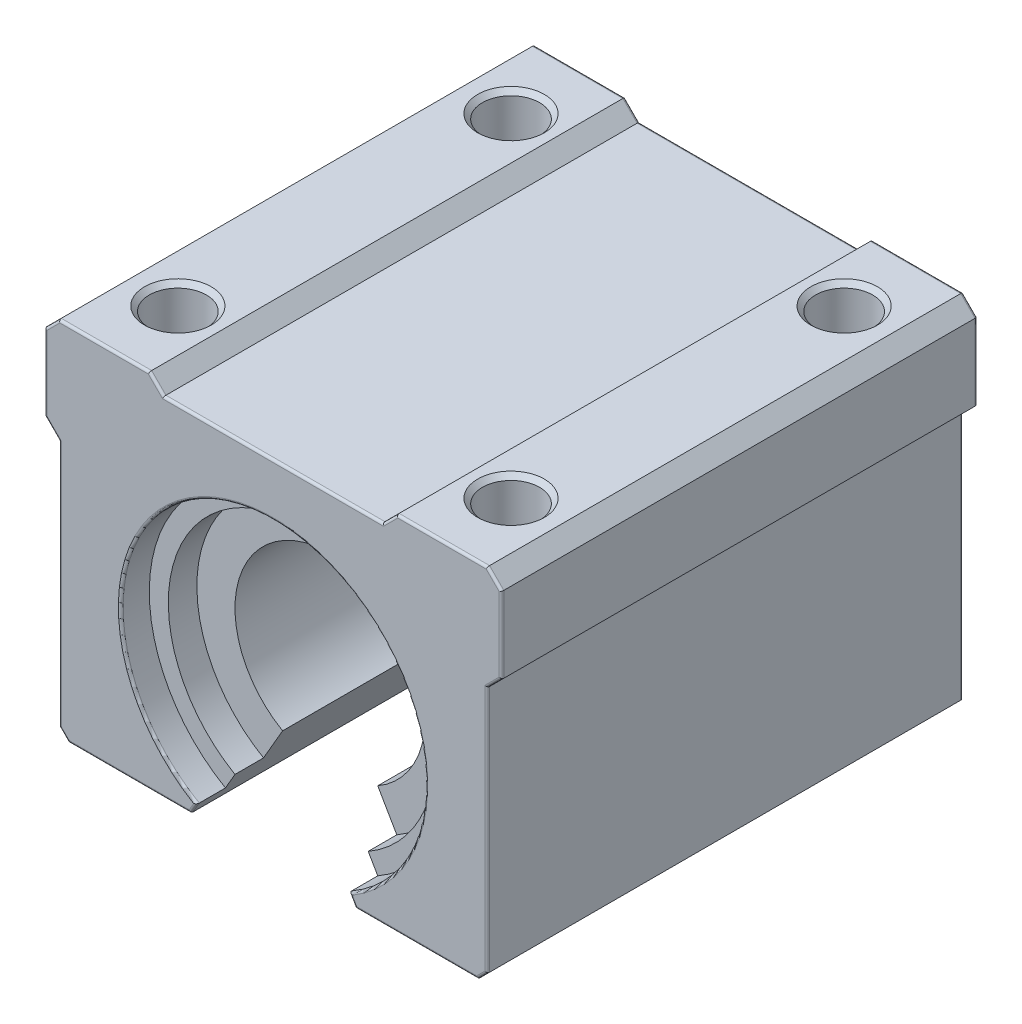
SolidWorks part; units mm, degrees
ref_plane "Front Plane" through (0, 0, 0) normal (0, 0, 1) x (1, 0, 0)
ref_plane "Top Plane" through (0, 0, 0) normal (0, 1, 0) x (1, 0, 0)
ref_plane "Right Plane" through (0, 0, 0) normal (1, 0, 0) x (0, 0, -1)
sketch "Sketch1" plane through (0, 0, 0) normal (0, 0, 1) x (1, 0, 0)
  line L0 (0, 29.1887) -> (0, -22.3517) construction
  line L1 (-34.9739, 0) -> (34.4479, 0) construction
  line L2 (-22.5, 12) -> (-22.5, -15)
  line L3 (24, 12) -> (22.5, 12)
  line L4 (24, 12) -> (24, 23)
  line L5 (24, 23) -> (11.5, 23)
  line L6 (-24, 12) -> (-24, 23)
  line L7 (24, 12) -> (-24, 23) construction
  line L8 (24, 23) -> (-24, 12) construction
  line L9 (-22.5, -15) -> (22.5, -15)
  line L10 (22.5, 12) -> (22.5, -15)
  line L11 (-22.5, 12) -> (-24, 12)
  line L12 (11.5, 21.5) -> (-11.5, 21.5)
  line L13 (-11.5, 21.5) -> (-11.5, 23)
  line L14 (11.5, 21.5) -> (11.5, 23)
  line L15 (-11.5, 23) -> (-24, 23)
  circle A0 centre (0, 0) radius 10 construction
  point P7 (0, 17.5)
  point P18 (0, -15)
  point P22 (0, 21.5)
  dimension "D1" = 20
  dimension "D4" = 23
  dimension "D2" = 48
  dimension "D3" = 11
  dimension "D5" = 38
  dimension "D6" = 22.5
  dimension "D7" = 23
  dimension "D8" = 1.5
  dimension "D9" = 1.5
extrude "Boss-Extrude2" add sketch "Sketch1" along normal mid plane 50
chamfer "Chamfer3" distance 1.5 angle 45 6 edges at (24, 23, 0) (24, 12, 0) (11.5, 23, 0) (-11.5, 23, 0) (-24, 12, 0) (-24, 23, 0)
chamfer "Chamfer4" distance 1 angle 45 2 edges at (22.5, -15, 0) (-22.5, -15, 0)
sketch "Sketch3" plane through (0, 21.5, 0) normal (0, 1, 0) x (1, 0, 0)
  line L0 (0, 31.926) -> (0, -36.2484) construction
  line L1 (42.0099, 0) -> (-40.1024, 0) construction
  circle A0 centre (-17.5, 17.5) radius 3
  circle A1 centre (17.5, 17.5) radius 3
  circle A2 centre (17.5, -17.5) radius 3
  circle A3 centre (-17.5, -17.5) radius 3
  dimension "D1" = 6
  dimension "D2" = 35
  dimension "D3" = 35
extrude "Cut-Extrude6" cut sketch "Sketch3" against normal blind 10.5 and the other way up to next
sketch "Sketch4" plane through (0, 0, 25) normal (0, 0, 1) x (1, 0, 0)
  circle A0 centre (0, 0) radius 10
  dimension "D1" = 20
extrude "Cut-Extrude8" cut sketch "Sketch4" against normal through all both
sketch "Sketch6" plane through (0, 0, 25) normal (0, 0, 1) x (1, 0, 0)
  line L0 (0, 22.6334) -> (0, -18.7712) construction
  line L1 (9.0802, -15.7273) -> (-9.0802, -15.7273)
  line L2 (-9.0802, -15.7273) -> (-5, -8.6603)
  line L3 (-5, -8.6603) -> (5, -8.6603)
  line L4 (9.0802, -15.7273) -> (5, -8.6603)
  line L5 (24, 13.5) -> (24, 21.5) construction
  circle A1 centre (0, 0) radius 10 construction
  point P10 (0, -15.7273)
  point P11 (0, -8.6603)
  dimension "D1" = 10
  dimension "D2" = 60
  dimension "D3" = 14.9198
extrude "Cut-Extrude9" cut sketch "Sketch6" against normal through all both
sketch "Sketch7" plane through (0, 0, 25) normal (0, 0, 1) x (1, 0, 0)
  circle A0 centre (0, 0) radius 16
  dimension "D1" = 32
extrude "Cut-Extrude10" cut sketch "Sketch7" against normal blind 3
sketch "Sketch8" plane through (0, 0, -25) normal (0, 0, -1) x (-1, 0, 0)
  circle A0 centre (0, 0) radius 16
  dimension "D1" = 32
extrude "Cut-Extrude11" cut sketch "Sketch8" against normal blind 3
sketch "Sketch9" plane through (0, 0, 22) normal (0, 0, 1) x (1, 0, 0)
  circle A0 centre (0, 0) radius 14
  dimension "D1" = 28
extrude "Cut-Extrude12" cut sketch "Sketch9" against normal blind 3
sketch "Sketch10" plane through (0, 0, -22) normal (0, 0, -1) x (-1, 0, 0)
  circle A0 centre (0, 0) radius 14
  dimension "D1" = 28
extrude "Cut-Extrude13" cut sketch "Sketch10" against normal blind 3
chamfer "Chamfer5" distance 0.5 angle 45 4 edges at (17.5, 23, 14.5) (17.5, 23, -20.5) (-14.5, 23, -17.5) (-14.5, 23, 17.5)
fillet "Fillet1" radius 0.25 20 edges at (15.0801, -15, -25) (22, -14.5, -25) (22.5, -1, -25) (23.25, 12.75, -25) (24, 17.5, -25) (23.25, 22.25, -25) (17.75, 23, -25) (12.25, 22.25, -25) (0, 21.5, -25) (-12.25, 22.25, -25) (-17.75, 23, -25) (-23.25, 22.25, -25) (-24, 17.5, -25) (-23.25, 12.75, -25) (-22.5, -1, -25) (-22, -14.5, -25) (-15.0801, -15, -25) (-8.3301, -14.4282, -25) (0, 16, -25) (8.3301, -14.4282, -25)
fillet "Fillet3" radius 0.25 20 edges at (-8.3301, -14.4282, 25) (-15.0801, -15, 25) (-22, -14.5, 25) (-22.5, -1, 25) (-23.25, 12.75, 25) (-24, 17.5, 25) (-23.25, 22.25, 25) (-17.75, 23, 25) (-12.25, 22.25, 25) (0, 21.5, 25) (12.25, 22.25, 25) (17.75, 23, 25) (23.25, 22.25, 25) (24, 17.5, 25) (23.25, 12.75, 25) (22.5, -1, 25) (22, -14.5, 25) (15.0801, -15, 25) (8.3301, -14.4282, 25) (0, 16, 25)
